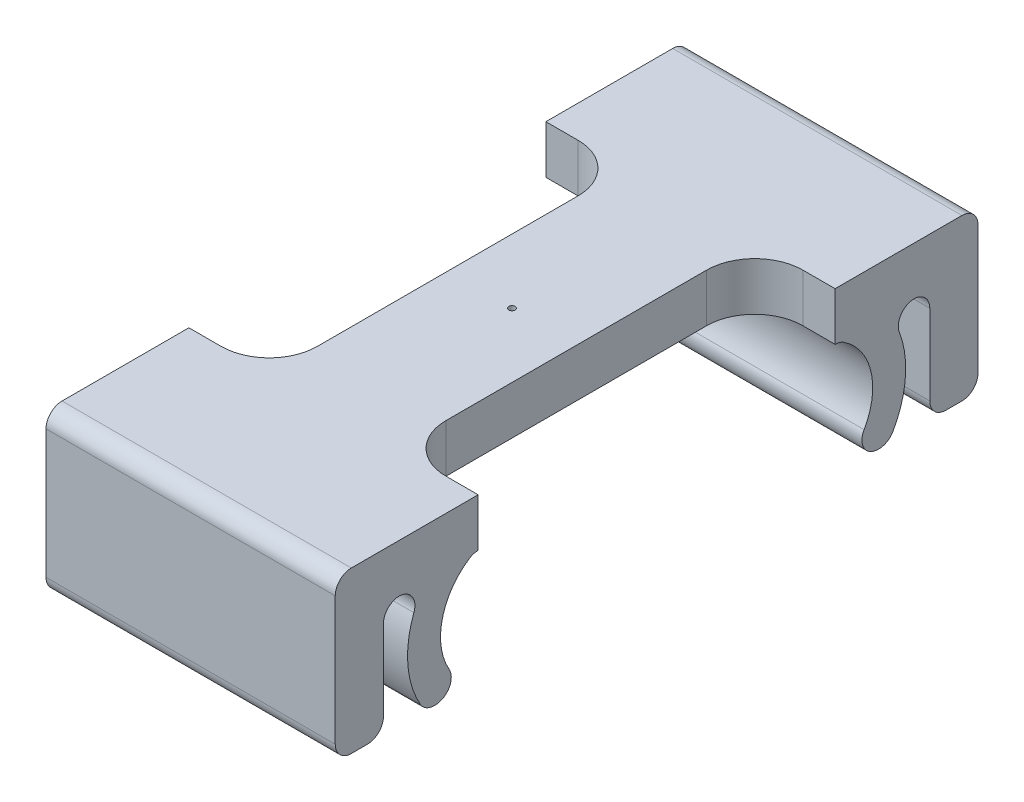
SolidWorks part; units mm, degrees
ref_plane "Спереди" through (0, 0, 0) normal (0, 0, 1) x (1, 0, 0)
ref_plane "Сверху" through (0, 0, 0) normal (0, 1, 0) x (1, 0, 0)
ref_plane "Справа" through (0, 0, 0) normal (1, 0, 0) x (0, 0, -1)
sketch "Эскиз1" plane through (22.5, -18, -41) normal (1, 0, 0) x (0, -1, 0)
  line L0 (-22, -4.5) -> (-56.5, -4.5) construction
  line L1 (-57.5, -2.5) -> (-20, -2.5) construction
  line L2 (-22, -4.5) -> (-57.5, -4.5) construction
  line L3 (-57.5, -2.5) -> (-20, -2.5) construction
  line L4 (-57.5, -2.5) -> (-57.5, -4.5) construction
  line L5 (-57.5, -2.5) -> (-57.5, -4.5) construction
  line L6 (-51, -2.5) -> (-51, 0.5)
  line L7 (-51, 0.5) -> (-61, 0.5)
  line L8 (-64.4379, -19.5) -> (-52.2737, -19.5) construction
  line L9 (-61, 0.5) -> (-61, -39.5)
  line L10 (-51, -2.5) -> (-58, -2.5)
  line L11 (-58, -2.5) -> (-58, -5.1149)
  line L12 (-51, -5.1149) -> (-51, -8.1149)
  line L13 (-58, -8.1149) -> (-58, -30.8851)
  line L14 (-54.5, -2.5) -> (-54.5, -10.0514) construction
  line L15 (-54.5, -4) -> (-61, -4) construction
  line L16 (-54.5, -35) -> (-61, -35) construction
  line L17 (-54.5, -36.5) -> (-54.5, -28.9486) construction
  line L18 (-57.5, -36.5) -> (-57.5, -34.5) construction
  line L19 (-51, -33.8851) -> (-51, -30.8851)
  line L20 (-58, -36.5) -> (-58, -33.8851)
  line L21 (-51, -36.5) -> (-58, -36.5)
  line L22 (-51, -39.5) -> (-61, -39.5)
  line L23 (-51, -36.5) -> (-51, -39.5)
  arc A0 (-58, -5.1149) -> (-51, -5.1149) centre (-54.5, -10.0514) cw
  arc A1 (-58, -8.1149) -> (-51, -8.1149) centre (-54.5, -10.0514) cw
  arc A2 (-58, -30.8851) -> (-51, -30.8851) centre (-54.5, -28.9486) ccw
  arc A3 (-58, -33.8851) -> (-51, -33.8851) centre (-54.5, -28.9486) ccw
  point P31 (-58, -19.5)
  point P34 (-61, -19.5)
  dimension "D6" = 1.5
  dimension "D8" = 4
  dimension "D1" = 17
  dimension "D2" = 0.5
  dimension "D3" = 10
  dimension "D4" = 3
  dimension "D5" = 3
  dimension "D7" = 3
  dimension "D9" = 34
extrude "Бобышка-Вытянуть1" add sketch "Эскиз1" along normal blind 4 and the other way blind 4
fillet "Скругление4" radius 1 16 edges at (22.5, 40, -10.1149) (22.5, 40, -32.8851) (22.5, 40, -38.5) (22.5, 40, -35.8851) (22.5, 40, -4.5) (22.5, 40, -7.1149) (22.5, 43, -1.5) (22.5, 43, -41.5) (22.5, 33, -41.5) (22.5, 33, -38.5) (22.5, 33, -35.8851) (22.5, 33, -32.8851) (22.5, 33, -10.1149) (22.5, 33, -7.1149) (22.5, 33, -4.5) (22.5, 33, -1.5)
sketch "Эскиз3" plane through (26.5, 0, 0) normal (1, 0, 0) x (0, 0, -1)
  line L0 (10.393, 40) -> (10.393, 43)
  line L1 (32.607, 40) -> (32.607, 43)
  line L2 (10.393, 43) -> (2.5, 43)
  line L10 (40.5, 43) -> (2.5, 43)
  line L11 (1.5, 42) -> (1.5, 34)
  line L12 (2.5, 33) -> (3.5, 33)
  line L13 (4.5, 34) -> (4.5, 39)
  line L14 (7.662, 33) -> (7.7212, 33)
  line L15 (10.393, 40) -> (32.607, 40)
  line L16 (35.2788, 33) -> (35.338, 33)
  line L17 (38.5, 39) -> (38.5, 34)
  line L18 (39.5, 33) -> (40.5, 33)
  line L19 (41.5, 34) -> (41.5, 42)
  line L20 (40.5, 43) -> (32.607, 43)
  line L21 (1.5, 42) -> (1.5, 34)
  line L22 (2.5, 33) -> (3.5, 33)
  line L23 (4.5, 34) -> (4.5, 39)
  line L24 (7.662, 33) -> (7.7212, 33)
  line L26 (35.2788, 33) -> (35.338, 33)
  line L27 (38.5, 39) -> (38.5, 34)
  line L28 (39.5, 33) -> (40.5, 33)
  line L29 (41.5, 34) -> (41.5, 42)
  arc A20 (2.5, 43) -> (1.5, 42) centre (2.5, 42) ccw
  arc A21 (1.5, 34) -> (2.5, 33) centre (2.5, 34) ccw
  arc A22 (3.5, 33) -> (4.5, 34) centre (3.5, 34) ccw
  arc A23 (5.479, 39.9998) -> (4.5, 39) centre (5.5, 39) ccw
  arc A24 (6.3931, 38.6455) -> (5.479, 39.9998) centre (5.4581, 39) ccw
  arc A25 (6.3931, 38.6455) -> (6.7931, 33.5051) centre (12.0514, 36.5) ccw
  arc A26 (6.7931, 33.5051) -> (7.662, 33) centre (7.662, 34) ccw
  arc A27 (7.7212, 33) -> (8.5873, 34.5) centre (7.7212, 34) ccw
  arc A28 (9.8403, 39.8333) -> (8.5873, 34.5) centre (12.0514, 36.5) ccw
  arc A29 (10.393, 40) -> (9.8403, 39.8333) centre (10.393, 39) ccw
  arc A30 (33.1597, 39.8333) -> (32.607, 40) centre (32.607, 39) ccw
  arc A31 (34.4127, 34.5) -> (33.1597, 39.8333) centre (30.9486, 36.5) ccw
  arc A32 (34.4127, 34.5) -> (35.2788, 33) centre (35.2788, 34) ccw
  arc A33 (35.338, 33) -> (36.2069, 33.5051) centre (35.338, 34) ccw
  arc A34 (36.2069, 33.5051) -> (36.6069, 38.6455) centre (30.9486, 36.5) ccw
  arc A35 (37.521, 39.9998) -> (36.6069, 38.6455) centre (37.5419, 39) ccw
  arc A36 (38.5, 39) -> (37.521, 39.9998) centre (37.5, 39) ccw
  arc A37 (38.5, 34) -> (39.5, 33) centre (39.5, 34) ccw
  arc A38 (40.5, 33) -> (41.5, 34) centre (40.5, 34) ccw
  arc A39 (41.5, 42) -> (40.5, 43) centre (40.5, 42) ccw
  arc A40 (2.5, 43) -> (1.5, 42) centre (2.5, 42) ccw
  arc A41 (1.5, 34) -> (2.5, 33) centre (2.5, 34) ccw
  arc A42 (3.5, 33) -> (4.5, 34) centre (3.5, 34) ccw
  arc A43 (5.479, 39.9998) -> (4.5, 39) centre (5.5, 39) ccw
  arc A44 (6.3931, 38.6455) -> (5.479, 39.9998) centre (5.4581, 39) ccw
  arc A45 (6.3931, 38.6455) -> (6.7931, 33.5051) centre (12.0514, 36.5) ccw
  arc A46 (6.7931, 33.5051) -> (7.662, 33) centre (7.662, 34) ccw
  arc A47 (7.7212, 33) -> (8.5873, 34.5) centre (7.7212, 34) ccw
  arc A48 (9.8403, 39.8333) -> (8.5873, 34.5) centre (12.0514, 36.5) ccw
  arc A49 (10.393, 40) -> (9.8403, 39.8333) centre (10.393, 39) ccw
  arc A50 (33.1597, 39.8333) -> (32.607, 40) centre (32.607, 39) ccw
  arc A51 (34.4127, 34.5) -> (33.1597, 39.8333) centre (30.9486, 36.5) ccw
  arc A52 (34.4127, 34.5) -> (35.2788, 33) centre (35.2788, 34) ccw
  arc A53 (35.338, 33) -> (36.2069, 33.5051) centre (35.338, 34) ccw
  arc A54 (36.2069, 33.5051) -> (36.6069, 38.6455) centre (30.9486, 36.5) ccw
  arc A55 (37.521, 39.9998) -> (36.6069, 38.6455) centre (37.5419, 39) ccw
  arc A56 (38.5, 39) -> (37.521, 39.9998) centre (37.5, 39) ccw
  arc A57 (38.5, 34) -> (39.5, 33) centre (39.5, 34) ccw
  arc A58 (40.5, 33) -> (41.5, 34) centre (40.5, 34) ccw
  arc A59 (41.5, 42) -> (40.5, 43) centre (40.5, 42) ccw
  dimension "D1" = 0
extrude "Бобышка-Вытянуть2" add sketch "Эскиз3" along normal blind 5
sketch "Эскиз4" plane through (0, 40, 0) normal (0, -1, 0) x (1, 0, 0)
  line L0 (22.5, -32.607) -> (22.5, -10.393) construction
  line L1 (18.5, -32.607) -> (26.5, -32.607) construction
  line L2 (26.5, -10.393) -> (18.5, -10.393) construction
ref_plane "Плоскость4" through (22.5, 0, 0) normal (1, 0, 0) x (0, 0, 1)
mirror "Зеркальное отражение1" about plane through (22.5, 0, 0) normal (1, 0, 0) of "Бобышка-Вытянуть2"
fillet "Скругление5" radius 3 4 edges at (18.5, 41.5, -10.393) (26.5, 41.5, -10.393)
sketch "Эскиз5" plane through (0, 43, 0) normal (0, 1, 0) x (1, 0, 0)
  line L0 (22.5, 2.5) -> (22.5, 40.5) construction
  line L1 (13.5, 2.5) -> (31.5, 2.5) construction
  line L2 (31.5, 40.5) -> (13.5, 40.5) construction
  circle A0 centre (22.5, 21.5) radius 0.2
  dimension "D1" = 0.4
extrude "Вырез-Вытянуть1" cut sketch "Эскиз5" against normal through all
